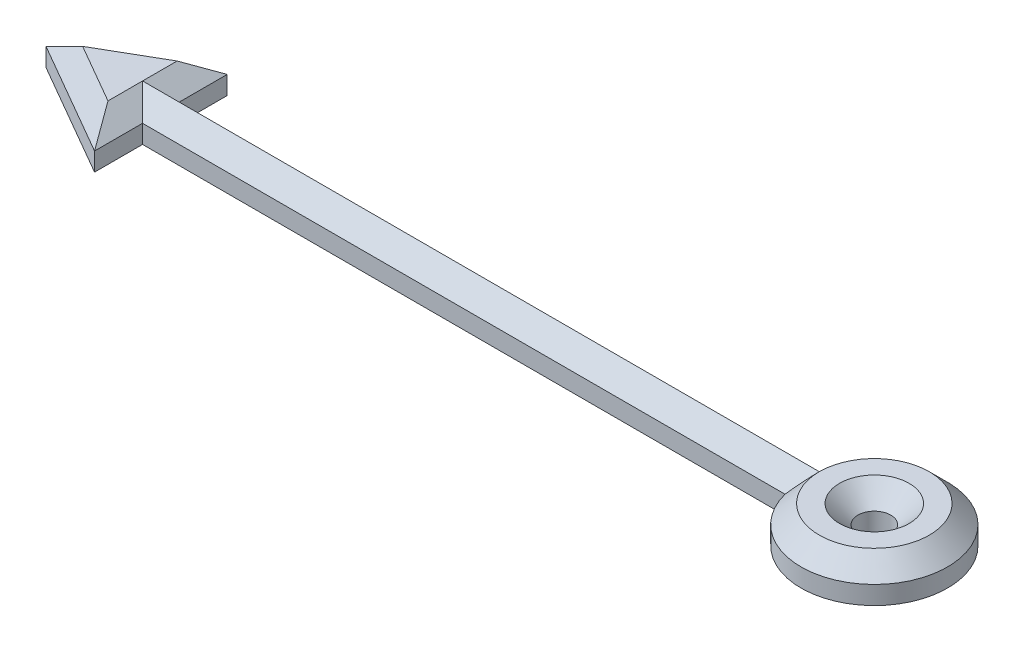
SolidWorks part; units mm, degrees
ref_plane "Alzado" through (0, 0, 0) normal (0, 0, 1) x (1, 0, 0)
ref_plane "Planta" through (0, 0, 0) normal (0, 1, 0) x (1, 0, 0)
ref_plane "Vista lateral" through (0, 0, 0) normal (1, 0, 0) x (0, 0, -1)
sketch "Croquis2" plane through (0, 0, 0) normal (0, 1, 0) x (1, 0, 0)
  line L0 (106.3863, 3.3432) -> (100.0863, -3.0841) construction
  line L1 (106.3863, -3.0841) -> (100.0863, 3.3432) construction
  line L2 (-91.3792, 5.1296) -> (-91.3792, 18.223)
  line L3 (83.8714, 5.1296) -> (-91.3792, 5.1296)
  line L4 (-91.3792, -4.8704) -> (83.8714, -4.8704)
  line L5 (-122.7181, 0.1296) -> (-91.3792, -17.9639)
  line L6 (-91.3792, -17.9639) -> (-91.3792, -4.8704)
  line L7 (-91.3792, 18.223) -> (-122.7181, 0.1296)
  line L8 (89.2363, -4.8704) -> (89.3784, -4.8704)
  circle A0 centre (103.2363, 0.1296) radius 4.5
  arc A1 (83.8714, -4.8704) -> (83.8714, 5.1296) centre (103.2363, 0.1296) ccw
  point P8 (99.3744, -9.5119)
  dimension "D1" = 9
  dimension "D2" = 40
extrude "Saliente-Extruir2" add sketch "Croquis2" along normal blind 10 contours L2 L7 L5 L6 L4 A1 L3 | A0
chamfer "Chaflán1" distance 5 angle 45 8 edges at (103.2363, 10, 4.3704) (123.2363, 10, -0.1296) (-3.7539, 10, 4.8704) (-91.3792, 10, 11.4172) (-107.0487, 10, 8.9172) (-107.0487, 10, -9.1763) (-91.3792, 10, -11.6763) (-3.7539, 10, -5.1296)
